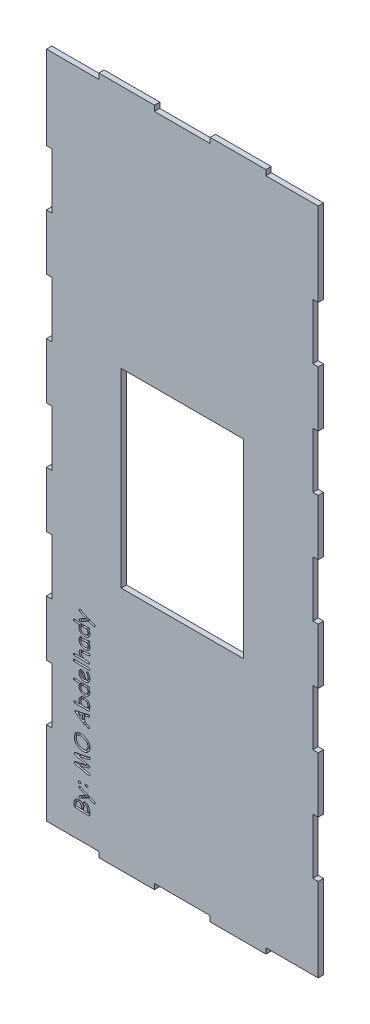
SolidWorks part; units mm, degrees
ref_plane "Front Plane" through (0, 0, 0) normal (0, 0, 1) x (1, 0, 0)
ref_plane "Top Plane" through (0, 0, 0) normal (0, 1, 0) x (1, 0, 0)
ref_plane "Right Plane" through (0, 0, 0) normal (1, 0, 0) x (0, 0, -1)
sketch "Sketch1" plane through (0, 0, 0) normal (0, 0, 1) x (1, 0, 0)
  line B0 (351.7636, 345.8843) -> (349.0607, 338.3403)
  line B1 (373.4521, 530.9583) -> (380.7137, 531.5169)
  line B2 (310.404, 529.7209) -> (312.7528, 529.9342)
  line B3 (314.6676, 657.3526) -> (309.122, 656.1739)
  line B4 (334.072, 630.7134) -> (275.0808, 643.876)
  line B5 (272.025, 667.7579) -> (347.9958, 684.4199)
  line B6 (347.9958, 684.4199) -> (367.3077, 689.5027)
  line B7 (280.051, 863.2247) -> (279.7964, 858.2878)
  line B8 (388.5312, 998.5826) -> (359.953, 1010.5295)
  line B9 (298.1365, 1067.9425) -> (341.0543, 1041.3167)
  line B10 (341.0543, 1041.3167) -> (334.072, 1075.4834)
  line B11 (334.072, 1075.4834) -> (298.1365, 1067.9425)
  line B12 (275.1838, 1155.1153) -> (314.9871, 1154.709)
  line B13 (266.1561, 1339.1682) -> (319.5489, 1335.6899)
  line B14 (346.9982, 1375.6214) -> (356.5084, 1372.7425)
  line B15 (265.6387, 1490.9155) -> (328.5793, 1490.0449)
  line B16 (321.6543, 1539.1501) -> (326.0657, 1539.2002)
  line B17 (266.1561, 1815.5462) -> (319.5489, 1812.0679)
  line B18 (1841.5, 2286) -> (698.5, 2286)
  line B19 (698.5, 2286) -> (698.5, 4064)
  line B20 (698.5, 4064) -> (1841.5, 4064)
  line B21 (1841.5, 4064) -> (1841.5, 2286)
  line B22 (0, 6299.2) -> (488.95, 6299.2)
  line B23 (488.95, 6299.2) -> (488.95, 6350)
  line B24 (488.95, 6350) -> (1009.65, 6350)
  line B25 (1009.65, 6350) -> (1009.65, 6299.2)
  line B26 (1009.65, 6299.2) -> (1530.35, 6299.2)
  line B27 (1530.35, 6299.2) -> (1530.35, 6350)
  line B28 (1530.35, 6350) -> (2051.05, 6350)
  line B29 (2051.05, 6350) -> (2051.05, 6299.2)
  line B30 (2051.05, 6299.2) -> (2540, 6299.2)
  line B31 (2540, 6299.2) -> (2540, 6038.85)
  line B32 (2540, 6038.85) -> (2540, 5518.15)
  line B33 (2540, 5518.15) -> (2489.2, 5518.15)
  line B34 (2489.2, 5518.15) -> (2489.2, 4997.45)
  line B35 (2489.2, 4997.45) -> (2540, 4997.45)
  line B36 (2540, 4997.45) -> (2540, 4476.75)
  line B37 (2540, 4476.75) -> (2489.2, 4476.75)
  line B38 (2489.2, 4476.75) -> (2489.2, 3956.05)
  line B39 (2489.2, 3956.05) -> (2540, 3956.05)
  line B40 (2540, 3956.05) -> (2540, 3435.35)
  line B41 (2540, 3435.35) -> (2489.2, 3435.35)
  line B42 (2489.2, 3435.35) -> (2489.2, 2914.65)
  line B43 (2489.2, 2914.65) -> (2540, 2914.65)
  line B44 (2540, 2914.65) -> (2540, 2393.95)
  line B45 (2540, 2393.95) -> (2489.2, 2393.95)
  line B46 (2489.2, 2393.95) -> (2489.2, 1873.25)
  line B47 (2489.2, 1873.25) -> (2540, 1873.25)
  line B48 (2540, 1873.25) -> (2540, 1352.55)
  line B49 (2540, 1352.55) -> (2489.2, 1352.55)
  line B50 (2489.2, 1352.55) -> (2489.2, 831.85)
  line B51 (2489.2, 831.85) -> (2540, 831.85)
  line B52 (2540, 831.85) -> (2540, 50.8)
  line B53 (2540, 50.8) -> (2051.05, 50.8)
  line B54 (2051.05, 50.8) -> (2051.05, 0)
  line B55 (2051.05, 0) -> (1530.35, 0)
  line B56 (1530.35, 0) -> (1530.35, 50.8)
  line B57 (1530.35, 50.8) -> (1009.65, 50.8)
  line B58 (1009.65, 50.8) -> (1009.65, 0)
  line B59 (1009.65, 0) -> (488.95, 0)
  line B60 (488.95, 0) -> (488.95, 50.8)
  line B61 (488.95, 50.8) -> (0, 50.8)
  line B62 (0, 50.8) -> (0, 311.15)
  line B63 (0, 311.15) -> (0, 831.85)
  line B64 (0, 831.85) -> (50.8, 831.85)
  line B65 (50.8, 831.85) -> (50.8, 1352.55)
  line B66 (50.8, 1352.55) -> (0, 1352.55)
  line B67 (0, 1352.55) -> (0, 1873.25)
  line B68 (0, 1873.25) -> (50.8, 1873.25)
  line B69 (50.8, 1873.25) -> (50.8, 2393.95)
  line B70 (50.8, 2393.95) -> (0, 2393.95)
  line B71 (0, 2393.95) -> (0, 2914.65)
  line B72 (0, 2914.65) -> (50.8, 2914.65)
  line B73 (50.8, 2914.65) -> (50.8, 3435.35)
  line B74 (50.8, 3435.35) -> (0, 3435.35)
  line B75 (0, 3435.35) -> (0, 3956.05)
  line B76 (0, 3956.05) -> (50.8, 3956.05)
  line B77 (50.8, 3956.05) -> (50.8, 4476.75)
  line B78 (50.8, 4476.75) -> (0, 4476.75)
  line B79 (0, 4476.75) -> (0, 4997.45)
  line B80 (0, 4997.45) -> (50.8, 4997.45)
  line B81 (50.8, 4997.45) -> (50.8, 5518.15)
  line B82 (50.8, 5518.15) -> (0, 5518.15)
  line B83 (0, 5518.15) -> (0, 6299.2)
  arc B84 (405.2913, 298.5878) -> (398.0297, 356.0288) centre (280.3738, 311.9755) ccw
  arc B85 (385.8578, 291.3263) -> (405.2913, 298.5878) centre (390.0848, 309.6489) ccw
  arc B86 (262.7929, 296.8556) -> (385.8578, 291.3263) centre (387.4587, 1699.2414) ccw
  arc B87 (257.5419, 307.7516) -> (262.7929, 296.8556) centre (269.1178, 306.6169) ccw
  arc B88 (275.4872, 368.4475) -> (257.5419, 307.7516) centre (314.1089, 324.0279) ccw
  arc B89 (335.2842, 359.0751) -> (275.4872, 368.4475) centre (300.6603, 333.613) ccw
  arc B90 (335.2842, 359.0751) -> (336.4058, 358.7244) centre (335.845, 358.8997) ccw
  arc B91 (359.2814, 384.7592) -> (336.4058, 358.7244) centre (377.5488, 345.6412) ccw
  arc B92 (386.509, 374.255) -> (359.2814, 384.7592) centre (364.9845, 359.0022) ccw
  arc B93 (398.0297, 356.0288) -> (386.509, 374.255) centre (327.3666, 324.1168) ccw
  arc B94 (274.4899, 327.9134) -> (275.7681, 313.6624) centre (305.484, 323.5107) ccw
  arc B95 (327.4621, 311.6214) -> (275.7681, 313.6624) centre (260.374, -731.9168) ccw
  arc B96 (327.4621, 311.6214) -> (314.2889, 353.5617) centre (286.6007, 321.826) ccw
  arc B97 (314.2889, 353.5617) -> (279.6494, 344.3475) centre (300.6456, 335.1332) ccw
  arc B98 (279.6494, 344.3475) -> (274.4899, 327.9134) centre (305.9823, 327.0533) ccw
  arc B99 (349.0607, 338.3403) -> (346.9194, 310.3181) centre (624.5985, 303.193) ccw
  arc B100 (346.9194, 310.3181) -> (387.1374, 309.7595) centre (382.0876, 1394.3009) ccw
  arc B101 (387.1374, 309.7595) -> (376.3274, 356.8273) centre (280.608, 310.0682) ccw
  arc B102 (376.3274, 356.8273) -> (364.6021, 367.4797) centre (357.7567, 348.1656) ccw
  arc B103 (364.6021, 367.4797) -> (351.7636, 345.8843) centre (385.1796, 340.6324) ccw
  arc B104 (318.711, 488.2267) -> (444.293, 433.2093) centre (992.0067, 1854.2483) ccw
  arc B105 (454.9121, 425.4999) -> (444.293, 433.2093) centre (442.8531, 420.0577) ccw
  arc B106 (440.4831, 414.7985) -> (454.9121, 425.4999) centre (445.4769, 423.1434) ccw
  arc B107 (392.8163, 433.7649) -> (440.4831, 414.7985) centre (601.9336, 889.9407) ccw
  arc B108 (315.7862, 393.9426) -> (392.8163, 433.7649) centre (-423.5086, 1918.4074) ccw
  arc B109 (313.1312, 412.9923) -> (315.7862, 393.9426) centre (315.248, 403.5775) ccw
  arc B110 (370.9385, 443.8194) -> (313.1312, 412.9923) centre (559.6476, 20.3357) ccw
  arc B111 (307.9738, 473.8484) -> (370.9385, 443.8194) centre (515.7301, 828.4446) ccw
  arc B112 (318.711, 488.2267) -> (307.9738, 473.8484) centre (314.2825, 480.3355) ccw
  arc B113 (380.7137, 512.4319) -> (380.7137, 531.5169) centre (380.5783, 521.9744) ccw
  arc B114 (364.445, 513.7469) -> (380.7137, 512.4319) centre (374.0442, 531.2129) ccw
  arc B115 (373.4521, 530.9583) -> (364.445, 513.7469) centre (372.3382, 520.5787) ccw
  arc B116 (312.7528, 510.8493) -> (312.7528, 529.9342) centre (312.6174, 520.3918) ccw
  arc B117 (296.8332, 518.6163) -> (312.7528, 510.8493) centre (307.8586, 521.0163) ccw
  arc B118 (310.404, 529.7209) -> (296.8332, 518.6163) centre (308.3142, 518.4301) ccw
  arc B119 (396.5216, 746.7947) -> (409.4807, 758.2084) centre (394.5806, 762.0622) ccw
  arc B120 (307.6324, 729.4414) -> (396.5216, 746.7947) centre (136.2036, 1843.8903) ccw
  arc B121 (399.1236, 697.9648) -> (307.6324, 729.4414) centre (-34.792, -414.5707) ccw
  arc B122 (400.6923, 679.9183) -> (399.1236, 697.9648) centre (394.7175, 688.4904) ccw
  arc B123 (314.6676, 657.3526) -> (400.6923, 679.9183) centre (236.5032, 1130.5841) ccw
  arc B124 (309.122, 656.1739) -> (400.5434, 636.158) centre (987.4023, 3535.3911) ccw
  arc B125 (395.1836, 617.5818) -> (400.5434, 636.158) centre (397.5492, 626.9606) ccw
  arc B126 (334.072, 630.7134) -> (395.1836, 617.5818) centre (429.4858, 925.9846) ccw
  arc B127 (261.089, 654.4852) -> (275.0808, 643.876) centre (278.8633, 663.3956) ccw
  arc B128 (272.025, 667.7579) -> (261.089, 654.4852) centre (272.1818, 656.487) ccw
  arc B129 (367.3077, 689.5027) -> (269.323, 719.0378) centre (4.0004, -338.4924) ccw
  arc B130 (260.3225, 734.6997) -> (269.323, 719.0378) centre (271.0609, 730.4536) ccw
  arc B131 (286.6028, 744.6783) -> (260.3225, 734.6997) centre (286.6072, 705.0705) ccw
  arc B132 (286.6028, 744.6783) -> (392.7733, 766.4439) centre (150.42, 1678.7915) ccw
  arc B133 (409.4807, 758.2084) -> (392.7733, 766.4439) centre (398.4034, 756.8007) ccw
  arc B134 (367.119, 789.1656) -> (407.4326, 849.909) centre (345.3379, 847.3702) ccw
  arc B135 (267.7532, 829.646) -> (367.119, 789.1656) centre (344.8796, 876.7705) ccw
  arc B136 (274.4899, 903.8123) -> (267.7532, 829.646) centre (331.9824, 861.201) ccw
  arc B137 (317.2275, 919.1905) -> (274.4899, 903.8123) centre (315.4214, 857.1345) ccw
  arc B138 (400.0313, 878.8157) -> (317.2275, 919.1905) centre (322.596, 825.103) ccw
  arc B139 (407.4326, 849.909) -> (400.0313, 878.8157) centre (344.4493, 849.1837) ccw
  arc B140 (279.7964, 858.2878) -> (308.3941, 816.1354) centre (331.1675, 862.3628) ccw
  arc B141 (308.3941, 816.1354) -> (365.324, 808.6845) centre (344.4506, 870.414) ccw
  arc B142 (365.324, 808.6845) -> (360.5612, 889.9613) centre (342.6156, 848.1317) ccw
  arc B143 (360.5612, 889.9613) -> (293.7959, 894.7644) centre (322.3888, 825.7835) ccw
  arc B144 (293.7959, 894.7644) -> (280.051, 863.2247) centre (317.4427, 865.6944) ccw
  arc B145 (391.057, 1088.8264) -> (404.5465, 1100.8058) centre (386.6442, 1107.3801) ccw
  arc B146 (353.25, 1079.8589) -> (391.057, 1088.8264) centre (307.7116, 1356.032) ccw
  arc B147 (353.25, 1079.8589) -> (363.6003, 1029.9814) centre (721.8663, 1130.3394) ccw
  arc B148 (400.8537, 1012.3661) -> (363.6003, 1029.9814) centre (272.0591, 788.1874) ccw
  arc B149 (388.5312, 998.5826) -> (400.8537, 1012.3661) centre (394.1989, 1005.9156) ccw
  arc B150 (345.2437, 1018.2287) -> (359.953, 1010.5295) centre (355.3739, 1019.6819) ccw
  arc B151 (267.3064, 1067.9309) -> (345.2437, 1018.2287) centre (614.8826, 1527.0023) ccw
  arc B152 (269.4593, 1080.6004) -> (267.3064, 1067.9309) centre (272.131, 1073.6287) ccw
  arc B153 (322.9314, 1092.1229) -> (269.4593, 1080.6004) centre (409.2936, 561.5122) ccw
  arc B154 (322.9314, 1092.1229) -> (380.3823, 1105.9038) centre (243.5639, 1549.6408) ccw
  arc B155 (398.8211, 1109.5802) -> (380.3823, 1105.9038) centre (396.1339, 1074.9797) ccw
  arc B156 (404.5465, 1100.8058) -> (398.8211, 1109.5802) centre (393.4752, 1099.8367) ccw
  arc B157 (400.0779, 1154.4297) -> (405.6637, 1180.3108) centre (321.6121, 1184.9081) ccw
  arc B158 (392.9016, 1138.7739) -> (400.0779, 1154.4297) centre (395.2671, 1147.1623) ccw
  arc B159 (264.959, 1139.124) -> (392.9016, 1138.7739) centre (335.4678, 3528.1348) ccw
  arc B160 (257.1505, 1154.3599) -> (264.959, 1139.124) centre (265.6266, 1149.0851) ccw
  arc B161 (275.1838, 1155.1153) -> (257.1505, 1154.3599) centre (267.6184, 1120.0905) ccw
  arc B162 (311.3621, 1207.5901) -> (314.9871, 1154.709) centre (349.9191, 1183.6684) ccw
  arc B163 (391.266, 1213.9305) -> (311.3621, 1207.5901) centre (354.2268, 1174.0531) ccw
  arc B164 (405.6637, 1180.3108) -> (391.266, 1213.9305) centre (357.2113, 1179.4537) ccw
  arc B165 (321.597, 1183.8484) -> (335.7155, 1154.795) centre (366.6156, 1187.7681) ccw
  arc B166 (335.7155, 1154.795) -> (381.2299, 1155.3734) centre (355.0297, 1425.9972) ccw
  arc B167 (381.2299, 1155.3734) -> (383.2273, 1196.7889) centre (345.2778, 1177.8632) ccw
  arc B168 (383.2273, 1196.7889) -> (340.9996, 1208.9439) centre (353.9527, 1174.5151) ccw
  arc B169 (340.9996, 1208.9439) -> (321.597, 1183.8484) centre (348.5751, 1183.0386) ccw
  arc B170 (319.5489, 1335.6899) -> (397.5875, 1337.3191) centre (345.115, 1980.9125) ccw
  arc B171 (396.5984, 1320.804) -> (397.5875, 1337.3191) centre (395.5746, 1329.1525) ccw
  arc B172 (396.5984, 1320.804) -> (401.6032, 1310.9332) centre (423.0518, 1328.0126) ccw
  arc B173 (353.2708, 1247.0277) -> (401.6032, 1310.9332) centre (360.534, 1291.7644) ccw
  arc B174 (305.0632, 1289.5937) -> (353.2708, 1247.0277) centre (352.4617, 1294.6929) ccw
  arc B175 (314.4285, 1319.3979) -> (305.0632, 1289.5937) centre (341.9552, 1294.3746) ccw
  arc B176 (258.0175, 1323.4534) -> (314.4285, 1319.3979) centre (314.7834, 1718.6893) ccw
  arc B177 (266.1561, 1339.1682) -> (258.0175, 1323.4534) centre (262.6115, 1331.0391) ccw
  arc B178 (321.9694, 1294.3547) -> (348.6516, 1263.9012) centre (351.2729, 1293.1137) ccw
  arc B179 (348.6516, 1263.9012) -> (388.3806, 1292.1631) centre (357.5217, 1293.4875) ccw
  arc B180 (388.3806, 1292.1631) -> (374.3222, 1317.8045) centre (356.5576, 1291.3901) ccw
  arc B181 (374.3222, 1317.8045) -> (336.0378, 1317.1814) centre (361.0009, 959.8116) ccw
  arc B182 (336.0378, 1317.1814) -> (321.9694, 1294.3547) centre (347.9447, 1294.0944) ccw
  arc B183 (382.6321, 1361.2991) -> (406.0361, 1405.4196) centre (358.7557, 1402.2321) ccw
  arc B184 (313.8234, 1376.7428) -> (382.6321, 1361.2991) centre (359.5017, 1419.2514) ccw
  arc B185 (313.323, 1433.3895) -> (313.8234, 1376.7428) centre (352.1736, 1405.4071) ccw
  arc B186 (348.9676, 1424.6907) -> (313.323, 1433.3895) centre (328.436, 1417.9385) ccw
  arc B187 (373.6383, 1374.3252) -> (348.9676, 1424.6907) centre (-582.7588, 937.0748) ccw
  arc B188 (373.6383, 1374.3252) -> (387.154, 1418.7657) centre (349.201, 1406.0328) ccw
  arc B189 (387.154, 1418.7657) -> (374.7787, 1438.5195) centre (348.9859, 1408.6076) ccw
  arc B190 (389.9943, 1446.7024) -> (374.7787, 1438.5195) centre (383.1235, 1441.2405) ccw
  arc B191 (406.0361, 1405.4196) -> (389.9943, 1446.7024) centre (346.7514, 1406.1407) ccw
  arc B192 (321.2246, 1402.906) -> (346.9982, 1375.6214) centre (351.5524, 1405.7388) ccw
  arc B193 (356.5084, 1372.7425) -> (328.6724, 1425.3424) centre (41.3027, 1239.5999) ccw
  arc B194 (328.6724, 1425.3424) -> (321.2246, 1402.906) centre (356.105, 1403.7818) ccw
  arc B195 (400.5201, 1486.9843) -> (328.5793, 1490.0449) centre (330.2212, 681.5992) ccw
  arc B196 (392.506, 1469.7704) -> (400.5201, 1486.9843) centre (395.9107, 1478.6578) ccw
  arc B197 (257.1971, 1473.206) -> (392.506, 1469.7704) centre (625.8186, 13325.0813) ccw
  arc B198 (265.6387, 1490.9155) -> (257.1971, 1473.206) centre (262.0525, 1481.7583) ccw
  arc B199 (394.8724, 1586.8845) -> (407.5256, 1596.548) centre (395.8975, 1598.658) ccw
  arc B200 (334.2349, 1582.2227) -> (394.8724, 1586.8845) centre (339.1032, 1915.5928) ccw
  arc B201 (334.2349, 1582.2227) -> (324.7914, 1570.5658) centre (334.3642, 1572.4643) ccw
  arc B202 (324.7914, 1570.5658) -> (349.0209, 1543.8609) centre (362.8315, 1580.7355) ccw
  arc B203 (349.0209, 1543.8609) -> (364.8261, 1539.6202) centre (362.7992, 1563.6392) ccw
  arc B204 (398.9917, 1536.1332) -> (364.8261, 1539.6202) centre (371.4326, 1435.2294) ccw
  arc B205 (389.5325, 1520.1153) -> (398.9917, 1536.1332) centre (393.8861, 1528.3463) ccw
  arc B206 (389.5325, 1520.1153) -> (272.87, 1521.5738) centre (313.2258, 83.0484) ccw
  arc B207 (255.6959, 1522.85) -> (272.87, 1521.5738) centre (265.8551, 1543.3688) ccw
  arc B208 (265.1909, 1539.1357) -> (255.6959, 1522.85) centre (262.8593, 1529.5843) ccw
  arc B209 (321.6543, 1539.1501) -> (265.1909, 1539.1357) centre (293.5689, 962.1542) ccw
  arc B210 (307.6254, 1585.2786) -> (326.0657, 1539.2002) centre (348.2134, 1574.7926) ccw
  arc B211 (332.0846, 1599.1466) -> (307.6254, 1585.2786) centre (329.9943, 1574.3298) ccw
  arc B212 (332.0846, 1599.1466) -> (399.1741, 1605.9276) centre (274.6231, 2502.9412) ccw
  arc B213 (407.5256, 1596.548) -> (399.1741, 1605.9276) centre (398.056, 1596.5241) ccw
  arc B214 (397.0057, 1688.8073) -> (407.898, 1701.4685) centre (367.9526, 1724.8174) ccw
  arc B215 (406.3743, 1656.3407) -> (397.0057, 1688.8073) centre (345.9133, 1656.479) ccw
  arc B216 (373.2674, 1621.7057) -> (406.3743, 1656.3407) centre (370.7142, 1657.2868) ccw
  arc B217 (305.1489, 1666.9678) -> (373.2674, 1621.7057) centre (359.9618, 1675.5705) ccw
  arc B218 (317.7742, 1703.0977) -> (305.1489, 1666.9678) centre (343.3884, 1673.8762) ccw
  arc B219 (328.8488, 1701.6351) -> (317.7742, 1703.0977) centre (320.7009, 1682.5999) ccw
  arc B220 (328.8488, 1701.6351) -> (381.1127, 1703.2373) centre (351.277, 1823.2471) ccw
  arc B221 (400.4658, 1709.9093) -> (381.1127, 1703.2373) centre (425.1054, 1607.0336) ccw
  arc B222 (407.898, 1701.4685) -> (400.4658, 1709.9093) centre (399.1702, 1701.276) ccw
  arc B223 (343.1955, 1682.1043) -> (324.246, 1683.6108) centre (325.0364, 1573.6199) ccw
  arc B224 (324.246, 1683.6108) -> (331.1375, 1651.1689) centre (348.6319, 1671.838) ccw
  arc B225 (331.1375, 1651.1689) -> (382.8549, 1644.3068) centre (361.5327, 1681.9283) ccw
  arc B226 (382.8549, 1644.3068) -> (383.5066, 1680.6294) centre (365.0461, 1662.7935) ccw
  arc B227 (383.5066, 1680.6294) -> (378.3058, 1684.8919) centre (377.7773, 1678.9429) ccw
  arc B228 (343.1955, 1682.1043) -> (378.3058, 1684.8919) centre (323.8548, 2148.208) ccw
  arc B229 (319.5489, 1812.0679) -> (397.5875, 1813.6971) centre (345.115, 2457.2906) ccw
  arc B230 (396.5984, 1797.182) -> (397.5875, 1813.6971) centre (395.5746, 1805.5305) ccw
  arc B231 (396.5984, 1797.182) -> (401.6032, 1787.3112) centre (423.0518, 1804.3906) ccw
  arc B232 (353.2708, 1723.4057) -> (401.6032, 1787.3112) centre (360.534, 1768.1424) ccw
  arc B233 (305.0632, 1765.9717) -> (353.2708, 1723.4057) centre (352.4617, 1771.0709) ccw
  arc B234 (314.4285, 1795.7759) -> (305.0632, 1765.9717) centre (341.9552, 1770.7527) ccw
  arc B235 (258.0175, 1799.8314) -> (314.4285, 1795.7759) centre (314.7834, 2195.0673) ccw
  arc B236 (266.1561, 1815.5462) -> (258.0175, 1799.8314) centre (262.6115, 1807.4171) ccw
  arc B237 (321.9694, 1770.7327) -> (348.6516, 1740.2792) centre (351.2729, 1769.4917) ccw
  arc B238 (348.6516, 1740.2792) -> (388.3806, 1768.5411) centre (357.5217, 1769.8655) ccw
  arc B239 (388.3806, 1768.5411) -> (374.3222, 1794.1825) centre (356.5576, 1767.7681) ccw
  arc B240 (374.3222, 1794.1825) -> (336.0378, 1793.5594) centre (361.0009, 1436.1896) ccw
  arc B241 (336.0378, 1793.5594) -> (321.9694, 1770.7327) centre (347.9447, 1770.4724) ccw
  arc B242 (318.711, 1919.8743) -> (444.293, 1864.8569) centre (992.0067, 3285.896) ccw
  arc B243 (454.9121, 1857.1476) -> (444.293, 1864.8569) centre (442.8531, 1851.7054) ccw
  arc B244 (440.4831, 1846.4461) -> (454.9121, 1857.1476) centre (445.4769, 1854.791) ccw
  arc B245 (392.8163, 1865.4125) -> (440.4831, 1846.4461) centre (601.9335, 2321.5883) ccw
  arc B246 (315.7862, 1825.5902) -> (392.8163, 1865.4125) centre (-423.5086, 3350.055) ccw
  arc B247 (313.1312, 1844.64) -> (315.7862, 1825.5902) centre (315.248, 1835.2251) ccw
  arc B248 (370.9385, 1875.467) -> (313.1312, 1844.64) centre (559.6476, 1451.9833) ccw
  arc B249 (307.9738, 1905.496) -> (370.9385, 1875.467) centre (515.7301, 2260.0922) ccw
  arc B250 (318.711, 1919.8743) -> (307.9738, 1905.496) centre (314.2825, 1911.9831) ccw
sketch_block_instance "s2-1"
sketch_block "s2"
extrude "Boss-Extrude1" add sketch "Sketch1" along normal blind 50 contours B83 B82 B81 B80 B79 B78 B77 B76 B75 B74 B73 B72 B71 B70 B69 B68 B67 B66 B65 B64 B63 B62 B61 B60 B59 B58 B57 B56 B55 B54 B53 B52 B51 B50 B49 B48 B47 B46 B45 B44 B43 B42 B41 B40 B39 B38 B37 B36 B35 B34 B33 | B102 B103 B0 B99 B100 B101 | B97 B98 B94 B95 B96 | B143 B144 B7 B140 B141 B142 | B10 B11 B9 | B168 B169 B165 B166 B167 | B181 B182 B178 B179 B180 | B193 B194 B192 B14 | B228 B223 B224 B225 B226 B227 | B240 B241 B237 B238 B239 region at (366.5901, 333.5282, 0) region at (333.7529, 853.4633, 0) region at (324.4209, 1061.5809, 0) region at (335.5235, 1396.4983, 0) region at (244.475, 6230.8084, 0) region at (301.3997, 332.5866, 0) region at (355.1753, 1181.3728, 0) region at (355.1718, 1291.6139, 0) region at (357.1776, 1663.0802, 0) region at (355.1718, 1767.9919, 0)
extrude "Boss-Extrude2" add sketch "Sketch1<3>" along normal blind 30 contours B119 B133 B132 B131 B130 B129 B6 B5 B128 B127 B4 B126 B125 B124 B3 B123 B122 B121 B120 | B134 B139 B138 B137 B136 B135 B144 B143 B142 B141 B140 B7 | B104 B112 B111 B110 B109 B108 B107 B106 B105 | B84 B93 B92 B91 B90 B89 B88 B87 B86 B85 B103 B102 B101 B100 B99 B0 B98 B97 B96 B95 B94 | B2 B118 B117 B116 | B1 B115 B114 B113 | B145 B156 B155 B154 B153 B152 B151 B150 B8 B149 B148 B147 B146 B11 B10 B9 | B157 B164 B163 B162 B12 B161 B160 B159 B158 B169 B168 B167 B166 B165 | B13 B177 B176 B175 B174 B173 B172 B171 B170 B182 B181 B180 B179 B178 | B183 B191 B190 B189 B188 B187 B186 B185 B184 B194 B193 B14 B192 | B15 B198 B197 B196 B195 | B199 B213 B212 B211 B210 B16 B209 B208 B207 B206 B205 B204 B203 B202 B201 B200 | B242 B250 B249 B248 B247 B246 B245 B244 B243 | B17 B236 B235 B234 B233 B232 B231 B230 B229 B241 B240 B239 B238 B237 | B214 B222 B221 B220 B219 B218 B217 B216 B215 B223 B228 B227 B226 B225 B224 region at (375.948, 521.4392, 0) region at (309.5959, 520.0069, 0) region at (312.3368, 654.6838, 0) region at (340.0871, 1058.7432, 0) region at (295.0676, 1153.1608, 0) region at (292.7364, 1335.6475, 0) region at (328.995, 1480.5163, 0) region at (323.8398, 1540.9476, 0) region at (292.7364, 1812.0255, 0) region at (333.5649, 332.7622, 0) region at (367.7748, 439.3483, 0) region at (311.5276, 794.9023, 0) region at (355.7714, 1398.685, 0) region at (402.6885, 1672.8621, 0) region at (367.7748, 1870.996, 0)
sketch "Sketch1<3>" plane through (0, 0, 0) normal (0, 0, 1) x (1, 0, 0) same geometry as "Sketch1"
scale "Scale1" scale about centroid uniform scaling yes scale factor 0.04
